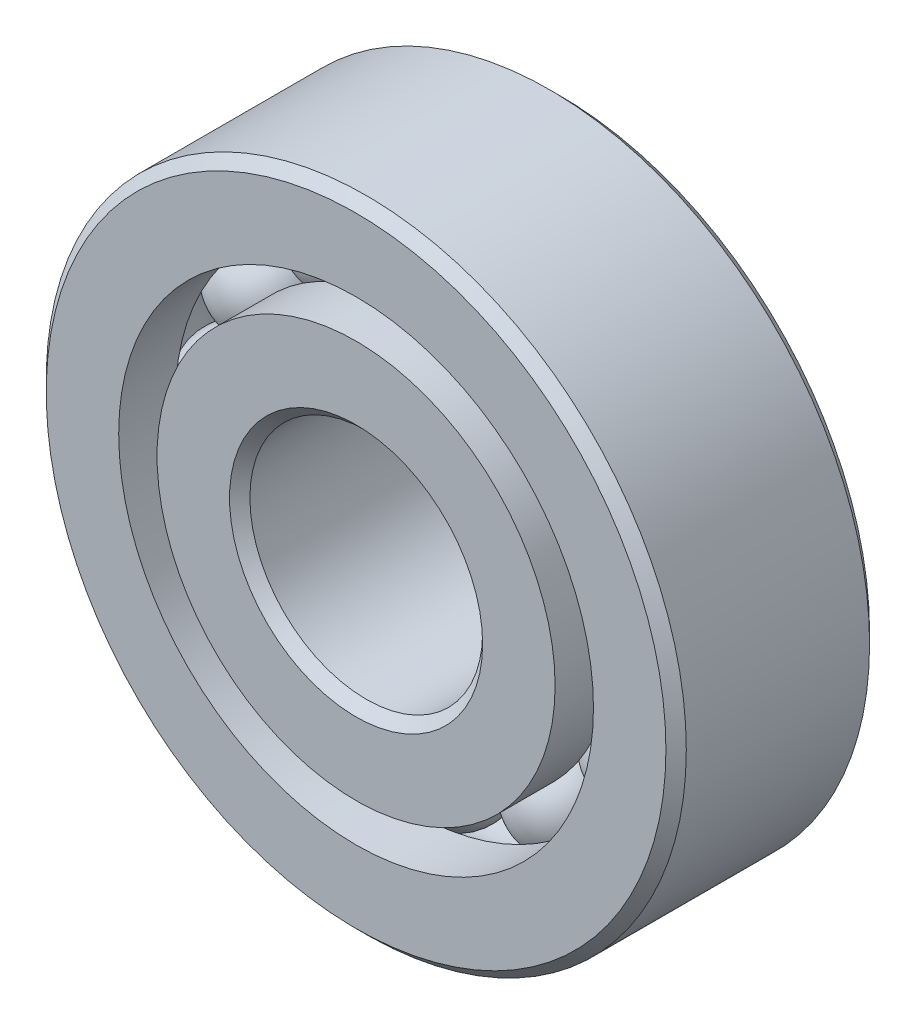
SolidWorks part; units mm, degrees
ref_plane "Front Plane" through (0, 0, 0) normal (0, 0, 1) x (1, 0, 0)
ref_plane "Top Plane" through (0, 0, 0) normal (0, 1, 0) x (1, 0, 0)
ref_plane "Right Plane" through (0, 0, 0) normal (1, 0, 0) x (0, 0, -1)
sketch "Sketch1" plane through (0, 0, 0) normal (1, 0, 0) x (0, 0, -1)
  line L0 (-3.5, 0) -> (3.5, 0) construction
  line L1 (0, 11) -> (0, -11) construction
  line L2 (3.15, 11) -> (-3.15, 11)
  line L3 (-3.15, 11) -> (-3.5, 10.65)
  line L4 (-3.5, 10.65) -> (-3.5, 8.1593)
  line L5 (-3.5, 8.1593) -> (-1.5556, 8.1593)
  line L6 (3.5, 8.1593) -> (1.5556, 8.1593)
  line L7 (3.5, 10.65) -> (3.5, 8.1593)
  line L8 (3.15, 11) -> (3.5, 10.65)
  line L9 (0, 11) -> (0, 7.5) construction
  line L10 (0, 7.5) -> (0, 4) construction
  arc A0 (-1.5556, 8.1593) -> (1.5556, 8.1593) centre (0, 7.5) cw
  point P14 (0, 4)
  dimension "Width" = 7
  dimension "OD" = 22
  dimension "D1" = 45
  dimension "D2" = 0.35
  dimension "Shaft Dia" = 8
  dimension "D3" = 3.1111
  dimension "D4" = 0.6593
revolve "Revolve1" add sketch "Sketch1" angle 360 about L0
sketch "Sketch3" plane through (0, 0, 0) normal (1, 0, 0) x (0, 0, -1)
  line L0 (-3.5, 6.8407) -> (-1.5556, 6.8407)
  line L1 (0, 11) -> (0, -11) construction
  line L2 (-3.5, 10.65) -> (-3.5, 8.1593) construction
  line L3 (-3.5, 6.8407) -> (-3.5, 4.35)
  line L4 (-3.15, 11) -> (-3.5, 10.65) construction
  line L5 (-3.5, 4.35) -> (-3.15, 4)
  line L6 (-3.15, 4) -> (3.15, 4)
  line L7 (3.15, 11) -> (3.15, -11) construction
  line L8 (3.15, 4) -> (3.5, 4.35)
  line L9 (3.5, -10.65) -> (3.5, 10.65) construction
  line L10 (3.5, 4.35) -> (3.5, 6.8407)
  line L11 (3.5, 6.8407) -> (1.5556, 6.8407)
  line L13 (3.15, 11) -> (3.5, 10.65) construction
  arc A0 (1.5556, 8.1593) -> (-1.5556, 8.1593) centre (0, 7.5) ccw construction
  arc A1 (1.5556, 6.8407) -> (-1.5556, 6.8407) centre (0, 7.5) cw
revolve "Revolve3" add sketch "Sketch3" angle 360 about L0
sketch "Sketch4" plane through (0, 0, 0) normal (1, 0, 0) x (0, 0, -1)
  line L0 (-1.6895, 7.5) -> (1.6895, 7.5)
  arc A2 (-1.6895, 7.5) -> (1.6895, 7.5) centre (0, 7.5) cw
  arc A3 (1.5556, 8.1593) -> (-1.5556, 8.1593) centre (0, 7.5) ccw construction
revolve "Revolve4" add sketch "Sketch4" angle 360 about L0
ref_axis "Axis1" through (0, 0, -3.5) along (0, 0, 1)
pattern_circular "CirPattern1" count 12 every 30 about axis through (0, 0, -3.5) along (0, 0, 1) of bodies 104
sketch "Sketch5" plane through (0, 0, 0) normal (1, 0, 0) x (0, 0, -1)
  line L0 (-3.5, 8.1593) -> (-1.5556, 8.1593) construction
  line L1 (-3.325, 8.1593) -> (-1.6895, 8.1593)
  line L2 (-3.325, 8.1593) -> (-3.325, 6.8407)
  line L3 (-3.325, 6.8407) -> (-1.6895, 6.8407)
  line L4 (-1.6895, 8.1593) -> (-1.6895, 6.8407)
  line L5 (-3.5, 6.8407) -> (-1.5556, 6.8407) construction
  line L6 (3.5, 8.1593) -> (1.5556, 8.1593) construction
  line L7 (3.325, 8.1593) -> (1.6895, 8.1593)
  line L8 (3.325, 8.1593) -> (3.325, 6.8407)
  line L9 (3.325, 6.8407) -> (1.6895, 6.8407)
  line L10 (1.6895, 8.1593) -> (1.6895, 6.8407)
  line L11 (3.5, 6.8407) -> (1.5556, 6.8407) construction
  line L12 (-3.15, 11) -> (-3.5, 10.65) construction
  point P18 (-3.325, 10.825)
equation "\"D2@Sketch1\" = \"Width@Sketch1\"*.05"
equation "\"D3@Sketch1\" = \"Width@Sketch1\"/2.25"
equation "\"D4@Sketch1\" = (((\"OD@Sketch1\"-\"Width@Sketch1\")/2)/3.25)/3.5"
equation "\"D2@CirPattern1\" = 360/\"Balls@CirPattern1\""
